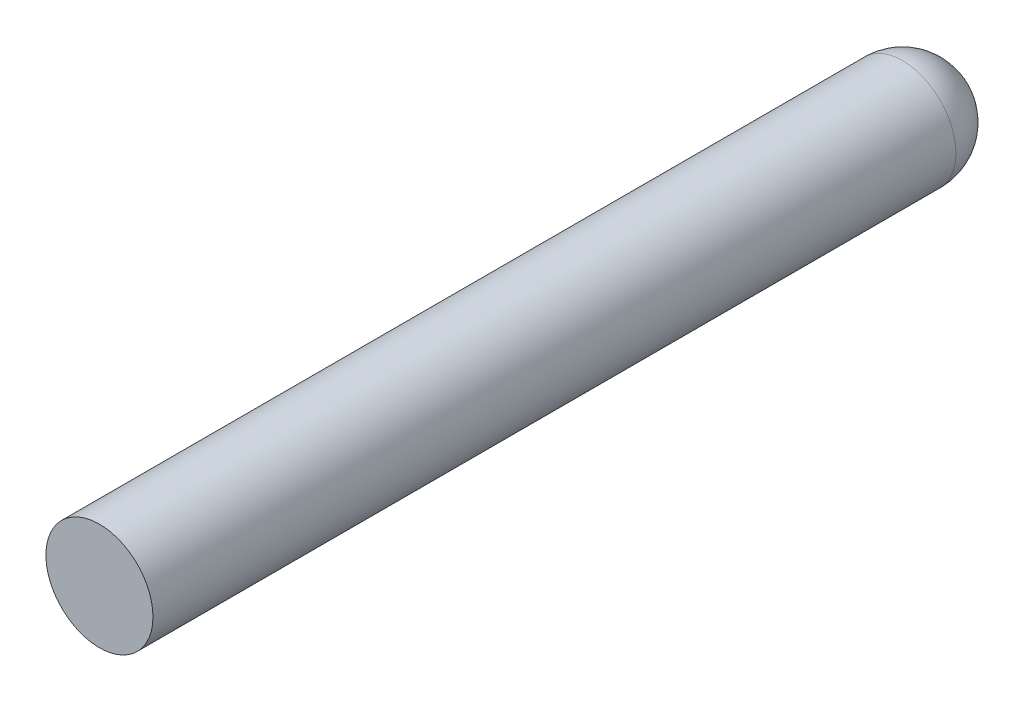
SolidWorks part; units mm, degrees
material "2014 Alloy"
ref_plane "Front Plane" through (0, 0, 0) normal (0, 0, 1) x (1, 0, 0)
ref_plane "Top Plane" through (0, 0, 0) normal (0, 1, 0) x (1, 0, 0)
ref_plane "Right Plane" through (0, 0, 0) normal (1, 0, 0) x (0, 0, -1)
sketch "Sketch1" plane through (0, 0, 0) normal (0, 0, 1) x (1, 0, 0)
  circle A0 centre (0, 0) radius 25.4
extrude "Boss-Extrude3" add sketch "Sketch1" along normal blind 381
sketch "Sketch4" plane through (0, 0, 0) normal (0, 1, 0) x (1, 0, 0)
  line L0 (25.4, 0) -> (-25.4, 0) construction
  line L1 (0, 0) -> (0, 25.4) construction
  line L2 (-25.4, 0) -> (25.4, 0)
  arc A0 (-25.4, 0) -> (25.4, 0) centre (0, 0) cw
revolve "Revolve3" add sketch "Sketch4" angle 360 about L1
